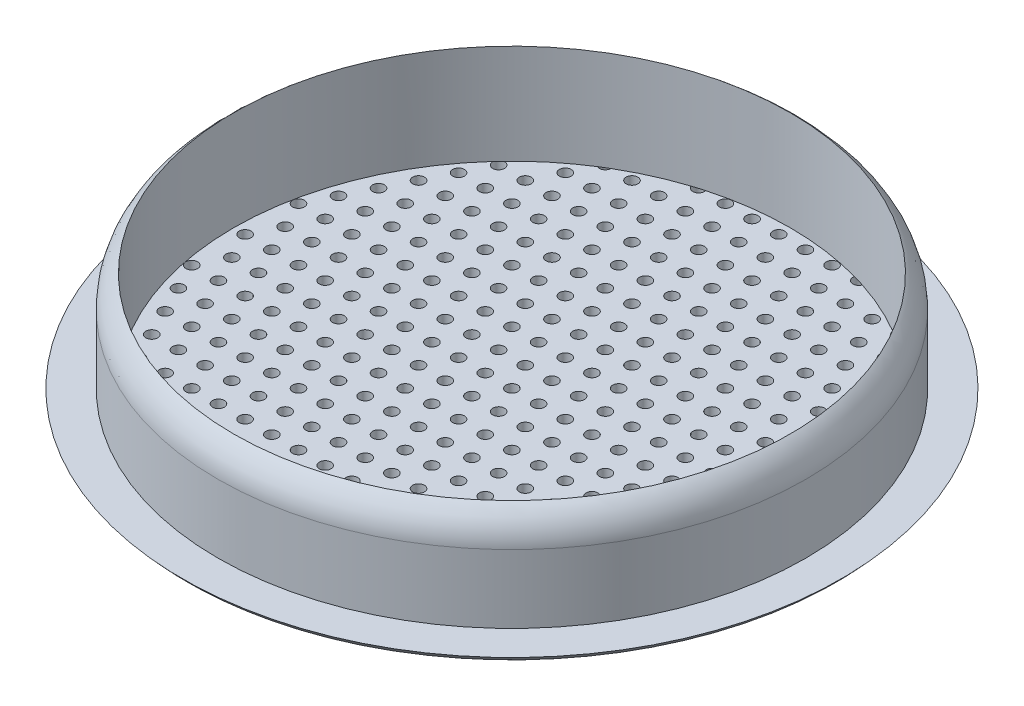
SolidWorks part; units mm, degrees
ref_plane "Front Plane" through (0, 0, 0) normal (0, 0, 1) x (1, 0, 0)
ref_plane "Top Plane" through (0, 0, 0) normal (0, 1, 0) x (1, 0, 0)
ref_plane "Right Plane" through (0, 0, 0) normal (1, 0, 0) x (0, 0, -1)
sketch "Sketch2" plane through (0, 0, 0) normal (0, 0, 1) x (1, 0, 0)
  line L0 (-35.465, 0) -> (-35.465, 12.7)
  line L1 (-35.465, 12.7) -> (-37.465, 12.7)
  line L2 (-37.465, 12.7) -> (-37.465, 0)
  line L3 (-37.465, 0) -> (-42, 0)
  line L4 (-42, 0) -> (-42, -2)
  line L5 (-42, -2) -> (0, -2)
  line L6 (0, -2) -> (0, 0)
  line L7 (0, 0) -> (-35.465, 0)
  line L8 (0, 0) -> (0, 8.6226) construction
  dimension "D1" = 2
  dimension "D2" = 2
  dimension "D3" = 84
  dimension "D4" = 74.93
  dimension "D5" = 12.7
revolve "Revolve1" add sketch "Sketch2" angle 360 about L8
sketch "Sketch3" plane through (0, 0, 0) normal (0, 1, 0) x (1, 0, 0)
  line L0 (0, 0) -> (-24.0588, 0) construction
  line L1 (0, -10.2) -> (0, 10.2) construction
  circle A0 centre (0, 0) radius 0.75
  circle A1 centre (3.4, 0) radius 0.75
  circle A2 centre (6.8, 0) radius 0.75
  circle A3 centre (10.2, 0) radius 0.75
  circle A4 centre (13.6, 0) radius 0.75
  circle A5 centre (17, 0) radius 0.75
  circle A6 centre (20.4, 0) radius 0.75
  circle A7 centre (23.8, 0) radius 0.75
  circle A8 centre (27.2, 0) radius 0.75
  circle A9 centre (30.6, 0) radius 0.75
  circle A10 centre (34, 0) radius 0.75
  circle A11 centre (3.4, 6.8) radius 0.75
  circle A12 centre (6.8, 6.8) radius 0.75
  circle A13 centre (10.2, 6.8) radius 0.75
  circle A14 centre (13.6, 6.8) radius 0.75
  circle A15 centre (17, 6.8) radius 0.75
  circle A16 centre (20.4, 6.8) radius 0.75
  circle A17 centre (23.8, 6.8) radius 0.75
  circle A18 centre (27.2, 6.8) radius 0.75
  circle A19 centre (30.6, 6.8) radius 0.75
  circle A20 centre (34, 6.8) radius 0.75
  circle A21 centre (3.4, 13.6) radius 0.75
  circle A22 centre (6.8, 13.6) radius 0.75
  circle A23 centre (10.2, 13.6) radius 0.75
  circle A24 centre (13.6, 13.6) radius 0.75
  circle A25 centre (17, 13.6) radius 0.75
  circle A26 centre (20.4, 13.6) radius 0.75
  circle A27 centre (23.8, 13.6) radius 0.75
  circle A28 centre (27.2, 13.6) radius 0.75
  circle A29 centre (30.6, 13.6) radius 0.75
  circle A30 centre (34, 13.6) radius 0.75 [skipped]
  circle A31 centre (3.4, 20.4) radius 0.75
  circle A32 centre (6.8, 20.4) radius 0.75
  circle A33 centre (10.2, 20.4) radius 0.75
  circle A34 centre (13.6, 20.4) radius 0.75
  circle A35 centre (17, 20.4) radius 0.75
  circle A36 centre (20.4, 20.4) radius 0.75
  circle A37 centre (23.8, 20.4) radius 0.75
  circle A38 centre (27.2, 20.4) radius 0.75
  circle A40 centre (34, 20.4) radius 0.75 [skipped]
  circle A41 centre (3.4, 27.2) radius 0.75
  circle A42 centre (6.8, 27.2) radius 0.75
  circle A43 centre (10.2, 27.2) radius 0.75
  circle A44 centre (13.6, 27.2) radius 0.75
  circle A45 centre (17, 27.2) radius 0.75
  circle A46 centre (20.4, 27.2) radius 0.75
  circle A48 centre (27.2, 27.2) radius 0.75 [skipped]
  circle A49 centre (30.6, 27.2) radius 0.75 [skipped]
  circle A50 centre (34, 27.2) radius 0.75 [skipped]
  circle A51 centre (3.4, 34) radius 0.75
  circle A52 centre (6.8, 34) radius 0.75
  circle A53 centre (10.2, 34) radius 0.75
  circle A54 centre (13.6, 34) radius 0.75
  circle A55 centre (17, 34) radius 0.75 [skipped]
  circle A56 centre (20.4, 34) radius 0.75 [skipped]
  circle A57 centre (23.8, 34) radius 0.75 [skipped]
  circle A58 centre (27.2, 34) radius 0.75 [skipped]
  circle A59 centre (30.6, 34) radius 0.75 [skipped]
  circle A60 centre (34, 34) radius 0.75 [skipped]
  circle A61 centre (0, 6.8) radius 0.75
  circle A62 centre (0, 13.6) radius 0.75
  circle A63 centre (0, 20.4) radius 0.75
  circle A64 centre (0, 27.2) radius 0.75
  circle A65 centre (0, 34) radius 0.75
  circle A66 centre (1.7, 3.4) radius 0.75
  circle A67 centre (5.1, 3.4) radius 0.75
  circle A68 centre (8.5, 3.4) radius 0.75
  circle A69 centre (11.9, 3.4) radius 0.75
  circle A70 centre (15.3, 3.4) radius 0.75
  circle A71 centre (18.7, 3.4) radius 0.75
  circle A72 centre (22.1, 3.4) radius 0.75
  circle A73 centre (25.5, 3.4) radius 0.75
  circle A74 centre (28.9, 3.4) radius 0.75
  circle A75 centre (32.3, 3.4) radius 0.75
  circle A77 centre (5.1, 10.2) radius 0.75
  circle A78 centre (8.5, 10.2) radius 0.75
  circle A79 centre (11.9, 10.2) radius 0.75
  circle A80 centre (15.3, 10.2) radius 0.75
  circle A81 centre (18.7, 10.2) radius 0.75
  circle A82 centre (22.1, 10.2) radius 0.75
  circle A83 centre (25.5, 10.2) radius 0.75
  circle A84 centre (28.9, 10.2) radius 0.75
  circle A85 centre (32.3, 10.2) radius 0.75
  circle A87 centre (5.1, 17) radius 0.75
  circle A88 centre (8.5, 17) radius 0.75
  circle A89 centre (11.9, 17) radius 0.75
  circle A90 centre (15.3, 17) radius 0.75
  circle A91 centre (18.7, 17) radius 0.75
  circle A92 centre (22.1, 17) radius 0.75
  circle A93 centre (25.5, 17) radius 0.75
  circle A94 centre (28.9, 17) radius 0.75
  circle A97 centre (5.1, 23.8) radius 0.75
  circle A98 centre (8.5, 23.8) radius 0.75
  circle A99 centre (11.9, 23.8) radius 0.75
  circle A100 centre (15.3, 23.8) radius 0.75
  circle A101 centre (18.7, 23.8) radius 0.75
  circle A102 centre (22.1, 23.8) radius 0.75
  circle A103 centre (25.5, 23.8) radius 0.75
  circle A107 centre (5.1, 30.6) radius 0.75
  circle A108 centre (8.5, 30.6) radius 0.75
  circle A109 centre (11.9, 30.6) radius 0.75
  circle A110 centre (15.3, 30.6) radius 0.75
  circle A111 centre (18.7, 30.6) radius 0.75
  circle A117 centre (1.7, 10.2) radius 0.75
  circle A118 centre (1.7, 17) radius 0.75
  circle A119 centre (1.7, 23.8) radius 0.75
  circle A120 centre (1.7, 30.6) radius 0.75
  circle A121 centre (35.7, 3.4) radius 0.75 [skipped]
  circle A122 centre (35.7, 10.2) radius 0.75 [skipped]
  circle A123 centre (32.3, 17) radius 0.75 [skipped]
  circle A124 centre (35.7, 17) radius 0.75 [skipped]
  circle A125 centre (32.3, 23.8) radius 0.75 [skipped]
  circle A126 centre (35.7, 23.8) radius 0.75 [skipped]
  circle A127 centre (32.3, 30.6) radius 0.75 [skipped]
  circle A128 centre (35.7, 30.6) radius 0.75 [skipped]
  circle A129 centre (25.5, 30.6) radius 0.75 [skipped]
  circle A130 centre (28.9, 30.6) radius 0.75 [skipped]
  circle A131 centre (30.6, 20.4) radius 0.75 [skipped]
  circle A132 centre (28.9, 23.8) radius 0.75 [skipped]
  circle A133 centre (23.8, 27.2) radius 0.75 [skipped]
  circle A134 centre (22.1, 30.6) radius 0.75 [skipped]
  circle A135 centre (-1.7, 30.6) radius 0.75
  circle A136 centre (-1.7, 23.8) radius 0.75
  circle A137 centre (-1.7, 17) radius 0.75
  circle A138 centre (-1.7, 10.2) radius 0.75
  circle A139 centre (-18.7, 30.6) radius 0.75
  circle A140 centre (-15.3, 30.6) radius 0.75
  circle A141 centre (-11.9, 30.6) radius 0.75
  circle A142 centre (-8.5, 30.6) radius 0.75
  circle A143 centre (-5.1, 30.6) radius 0.75
  circle A144 centre (-25.5, 23.8) radius 0.75
  circle A145 centre (-22.1, 23.8) radius 0.75
  circle A146 centre (-18.7, 23.8) radius 0.75
  circle A147 centre (-15.3, 23.8) radius 0.75
  circle A148 centre (-11.9, 23.8) radius 0.75
  circle A149 centre (-8.5, 23.8) radius 0.75
  circle A150 centre (-5.1, 23.8) radius 0.75
  circle A151 centre (-28.9, 17) radius 0.75
  circle A152 centre (-25.5, 17) radius 0.75
  circle A153 centre (-22.1, 17) radius 0.75
  circle A154 centre (-18.7, 17) radius 0.75
  circle A155 centre (-15.3, 17) radius 0.75
  circle A156 centre (-11.9, 17) radius 0.75
  circle A157 centre (-8.5, 17) radius 0.75
  circle A158 centre (-5.1, 17) radius 0.75
  circle A159 centre (-32.3, 10.2) radius 0.75
  circle A160 centre (-28.9, 10.2) radius 0.75
  circle A161 centre (-25.5, 10.2) radius 0.75
  circle A162 centre (-22.1, 10.2) radius 0.75
  circle A163 centre (-18.7, 10.2) radius 0.75
  circle A164 centre (-15.3, 10.2) radius 0.75
  circle A165 centre (-11.9, 10.2) radius 0.75
  circle A166 centre (-8.5, 10.2) radius 0.75
  circle A167 centre (-5.1, 10.2) radius 0.75
  circle A168 centre (-32.3, 3.4) radius 0.75
  circle A169 centre (-28.9, 3.4) radius 0.75
  circle A170 centre (-25.5, 3.4) radius 0.75
  circle A171 centre (-22.1, 3.4) radius 0.75
  circle A172 centre (-18.7, 3.4) radius 0.75
  circle A173 centre (-15.3, 3.4) radius 0.75
  circle A174 centre (-11.9, 3.4) radius 0.75
  circle A175 centre (-8.5, 3.4) radius 0.75
  circle A176 centre (-5.1, 3.4) radius 0.75
  circle A177 centre (-1.7, 3.4) radius 0.75
  circle A178 centre (-13.6, 34) radius 0.75
  circle A179 centre (-10.2, 34) radius 0.75
  circle A180 centre (-6.8, 34) radius 0.75
  circle A181 centre (-3.4, 34) radius 0.75
  circle A182 centre (-20.4, 27.2) radius 0.75
  circle A183 centre (-17, 27.2) radius 0.75
  circle A184 centre (-13.6, 27.2) radius 0.75
  circle A185 centre (-10.2, 27.2) radius 0.75
  circle A186 centre (-6.8, 27.2) radius 0.75
  circle A187 centre (-3.4, 27.2) radius 0.75
  circle A188 centre (-27.2, 20.4) radius 0.75
  circle A189 centre (-23.8, 20.4) radius 0.75
  circle A190 centre (-20.4, 20.4) radius 0.75
  circle A191 centre (-17, 20.4) radius 0.75
  circle A192 centre (-13.6, 20.4) radius 0.75
  circle A193 centre (-10.2, 20.4) radius 0.75
  circle A194 centre (-6.8, 20.4) radius 0.75
  circle A195 centre (-3.4, 20.4) radius 0.75
  circle A196 centre (-30.6, 13.6) radius 0.75
  circle A197 centre (-27.2, 13.6) radius 0.75
  circle A198 centre (-23.8, 13.6) radius 0.75
  circle A199 centre (-20.4, 13.6) radius 0.75
  circle A200 centre (-17, 13.6) radius 0.75
  circle A201 centre (-13.6, 13.6) radius 0.75
  circle A202 centre (-10.2, 13.6) radius 0.75
  circle A203 centre (-6.8, 13.6) radius 0.75
  circle A204 centre (-3.4, 13.6) radius 0.75
  circle A205 centre (-34, 6.8) radius 0.75
  circle A206 centre (-30.6, 6.8) radius 0.75
  circle A207 centre (-27.2, 6.8) radius 0.75
  circle A208 centre (-23.8, 6.8) radius 0.75
  circle A209 centre (-20.4, 6.8) radius 0.75
  circle A210 centre (-17, 6.8) radius 0.75
  circle A211 centre (-13.6, 6.8) radius 0.75
  circle A212 centre (-10.2, 6.8) radius 0.75
  circle A213 centre (-6.8, 6.8) radius 0.75
  circle A214 centre (-3.4, 6.8) radius 0.75
  circle A215 centre (-34, 0) radius 0.75
  circle A216 centre (-30.6, 0) radius 0.75
  circle A217 centre (-27.2, 0) radius 0.75
  circle A218 centre (-23.8, 0) radius 0.75
  circle A219 centre (-20.4, 0) radius 0.75
  circle A220 centre (-17, 0) radius 0.75
  circle A221 centre (-13.6, 0) radius 0.75
  circle A222 centre (-10.2, 0) radius 0.75
  circle A223 centre (-6.8, 0) radius 0.75
  circle A224 centre (-3.4, 0) radius 0.75
  circle A225 centre (-3.4, -6.8) radius 0.75
  circle A226 centre (-6.8, -6.8) radius 0.75
  circle A227 centre (-10.2, -6.8) radius 0.75
  circle A228 centre (-13.6, -6.8) radius 0.75
  circle A229 centre (-17, -6.8) radius 0.75
  circle A230 centre (-20.4, -6.8) radius 0.75
  circle A231 centre (-23.8, -6.8) radius 0.75
  circle A232 centre (-27.2, -6.8) radius 0.75
  circle A233 centre (-30.6, -6.8) radius 0.75
  circle A234 centre (-34, -6.8) radius 0.75
  circle A235 centre (-3.4, -13.6) radius 0.75
  circle A236 centre (-6.8, -13.6) radius 0.75
  circle A237 centre (-10.2, -13.6) radius 0.75
  circle A238 centre (-13.6, -13.6) radius 0.75
  circle A239 centre (-17, -13.6) radius 0.75
  circle A240 centre (-20.4, -13.6) radius 0.75
  circle A241 centre (-23.8, -13.6) radius 0.75
  circle A242 centre (-27.2, -13.6) radius 0.75
  circle A243 centre (-30.6, -13.6) radius 0.75
  circle A244 centre (-3.4, -20.4) radius 0.75
  circle A245 centre (-6.8, -20.4) radius 0.75
  circle A246 centre (-10.2, -20.4) radius 0.75
  circle A247 centre (-13.6, -20.4) radius 0.75
  circle A248 centre (-17, -20.4) radius 0.75
  circle A249 centre (-20.4, -20.4) radius 0.75
  circle A250 centre (-23.8, -20.4) radius 0.75
  circle A251 centre (-27.2, -20.4) radius 0.75
  circle A252 centre (-3.4, -27.2) radius 0.75
  circle A253 centre (-6.8, -27.2) radius 0.75
  circle A254 centre (-10.2, -27.2) radius 0.75
  circle A255 centre (-13.6, -27.2) radius 0.75
  circle A256 centre (-17, -27.2) radius 0.75
  circle A257 centre (-20.4, -27.2) radius 0.75
  circle A258 centre (-3.4, -34) radius 0.75
  circle A259 centre (-6.8, -34) radius 0.75
  circle A260 centre (-10.2, -34) radius 0.75
  circle A261 centre (-13.6, -34) radius 0.75
  circle A262 centre (-1.7, -3.4) radius 0.75
  circle A263 centre (-5.1, -3.4) radius 0.75
  circle A264 centre (-8.5, -3.4) radius 0.75
  circle A265 centre (-11.9, -3.4) radius 0.75
  circle A266 centre (-15.3, -3.4) radius 0.75
  circle A267 centre (-18.7, -3.4) radius 0.75
  circle A268 centre (-22.1, -3.4) radius 0.75
  circle A269 centre (-25.5, -3.4) radius 0.75
  circle A270 centre (-28.9, -3.4) radius 0.75
  circle A271 centre (-32.3, -3.4) radius 0.75
  circle A272 centre (-5.1, -10.2) radius 0.75
  circle A273 centre (-8.5, -10.2) radius 0.75
  circle A274 centre (-11.9, -10.2) radius 0.75
  circle A275 centre (-15.3, -10.2) radius 0.75
  circle A276 centre (-18.7, -10.2) radius 0.75
  circle A277 centre (-22.1, -10.2) radius 0.75
  circle A278 centre (-25.5, -10.2) radius 0.75
  circle A279 centre (-28.9, -10.2) radius 0.75
  circle A280 centre (-32.3, -10.2) radius 0.75
  circle A281 centre (-5.1, -17) radius 0.75
  circle A282 centre (-8.5, -17) radius 0.75
  circle A283 centre (-11.9, -17) radius 0.75
  circle A284 centre (-15.3, -17) radius 0.75
  circle A285 centre (-18.7, -17) radius 0.75
  circle A286 centre (-22.1, -17) radius 0.75
  circle A287 centre (-25.5, -17) radius 0.75
  circle A288 centre (-28.9, -17) radius 0.75
  circle A289 centre (-5.1, -23.8) radius 0.75
  circle A290 centre (-8.5, -23.8) radius 0.75
  circle A291 centre (-11.9, -23.8) radius 0.75
  circle A292 centre (-15.3, -23.8) radius 0.75
  circle A293 centre (-18.7, -23.8) radius 0.75
  circle A294 centre (-22.1, -23.8) radius 0.75
  circle A295 centre (-25.5, -23.8) radius 0.75
  circle A296 centre (-5.1, -30.6) radius 0.75
  circle A297 centre (-8.5, -30.6) radius 0.75
  circle A298 centre (-11.9, -30.6) radius 0.75
  circle A299 centre (-15.3, -30.6) radius 0.75
  circle A300 centre (-18.7, -30.6) radius 0.75
  circle A301 centre (-1.7, -10.2) radius 0.75
  circle A302 centre (-1.7, -17) radius 0.75
  circle A303 centre (-1.7, -23.8) radius 0.75
  circle A304 centre (-1.7, -30.6) radius 0.75
  circle A305 centre (1.7, -30.6) radius 0.75
  circle A306 centre (1.7, -23.8) radius 0.75
  circle A307 centre (1.7, -17) radius 0.75
  circle A308 centre (1.7, -10.2) radius 0.75
  circle A309 centre (18.7, -30.6) radius 0.75
  circle A310 centre (15.3, -30.6) radius 0.75
  circle A311 centre (11.9, -30.6) radius 0.75
  circle A312 centre (8.5, -30.6) radius 0.75
  circle A313 centre (5.1, -30.6) radius 0.75
  circle A314 centre (25.5, -23.8) radius 0.75
  circle A315 centre (22.1, -23.8) radius 0.75
  circle A316 centre (18.7, -23.8) radius 0.75
  circle A317 centre (15.3, -23.8) radius 0.75
  circle A318 centre (11.9, -23.8) radius 0.75
  circle A319 centre (8.5, -23.8) radius 0.75
  circle A320 centre (5.1, -23.8) radius 0.75
  circle A321 centre (28.9, -17) radius 0.75
  circle A322 centre (25.5, -17) radius 0.75
  circle A323 centre (22.1, -17) radius 0.75
  circle A324 centre (18.7, -17) radius 0.75
  circle A325 centre (15.3, -17) radius 0.75
  circle A326 centre (11.9, -17) radius 0.75
  circle A327 centre (8.5, -17) radius 0.75
  circle A328 centre (5.1, -17) radius 0.75
  circle A329 centre (32.3, -10.2) radius 0.75
  circle A330 centre (28.9, -10.2) radius 0.75
  circle A331 centre (25.5, -10.2) radius 0.75
  circle A332 centre (22.1, -10.2) radius 0.75
  circle A333 centre (18.7, -10.2) radius 0.75
  circle A334 centre (15.3, -10.2) radius 0.75
  circle A335 centre (11.9, -10.2) radius 0.75
  circle A336 centre (8.5, -10.2) radius 0.75
  circle A337 centre (5.1, -10.2) radius 0.75
  circle A338 centre (32.3, -3.4) radius 0.75
  circle A339 centre (28.9, -3.4) radius 0.75
  circle A340 centre (25.5, -3.4) radius 0.75
  circle A341 centre (22.1, -3.4) radius 0.75
  circle A342 centre (18.7, -3.4) radius 0.75
  circle A343 centre (15.3, -3.4) radius 0.75
  circle A344 centre (11.9, -3.4) radius 0.75
  circle A345 centre (8.5, -3.4) radius 0.75
  circle A346 centre (5.1, -3.4) radius 0.75
  circle A347 centre (1.7, -3.4) radius 0.75
  circle A348 centre (0, -34) radius 0.75
  circle A349 centre (0, -27.2) radius 0.75
  circle A350 centre (0, -20.4) radius 0.75
  circle A351 centre (0, -13.6) radius 0.75
  circle A352 centre (0, -6.8) radius 0.75
  circle A353 centre (13.6, -34) radius 0.75
  circle A354 centre (10.2, -34) radius 0.75
  circle A355 centre (6.8, -34) radius 0.75
  circle A356 centre (3.4, -34) radius 0.75
  circle A357 centre (20.4, -27.2) radius 0.75
  circle A358 centre (17, -27.2) radius 0.75
  circle A359 centre (13.6, -27.2) radius 0.75
  circle A360 centre (10.2, -27.2) radius 0.75
  circle A361 centre (6.8, -27.2) radius 0.75
  circle A362 centre (3.4, -27.2) radius 0.75
  circle A363 centre (27.2, -20.4) radius 0.75
  circle A364 centre (23.8, -20.4) radius 0.75
  circle A365 centre (20.4, -20.4) radius 0.75
  circle A366 centre (17, -20.4) radius 0.75
  circle A367 centre (13.6, -20.4) radius 0.75
  circle A368 centre (10.2, -20.4) radius 0.75
  circle A369 centre (6.8, -20.4) radius 0.75
  circle A370 centre (3.4, -20.4) radius 0.75
  circle A371 centre (30.6, -13.6) radius 0.75
  circle A372 centre (27.2, -13.6) radius 0.75
  circle A373 centre (23.8, -13.6) radius 0.75
  circle A374 centre (20.4, -13.6) radius 0.75
  circle A375 centre (17, -13.6) radius 0.75
  circle A376 centre (13.6, -13.6) radius 0.75
  circle A377 centre (10.2, -13.6) radius 0.75
  circle A378 centre (6.8, -13.6) radius 0.75
  circle A379 centre (3.4, -13.6) radius 0.75
  circle A380 centre (34, -6.8) radius 0.75
  circle A381 centre (30.6, -6.8) radius 0.75
  circle A382 centre (27.2, -6.8) radius 0.75
  circle A383 centre (23.8, -6.8) radius 0.75
  circle A384 centre (20.4, -6.8) radius 0.75
  circle A385 centre (17, -6.8) radius 0.75
  circle A386 centre (13.6, -6.8) radius 0.75
  circle A387 centre (10.2, -6.8) radius 0.75
  circle A388 centre (6.8, -6.8) radius 0.75
  circle A389 centre (3.4, -6.8) radius 0.75
  dimension "D1" = 1.5
  dimension "D4" = 1.5
  dimension "D5" = 3.4
  dimension "D6" = 1.7
  dimension "D2" = 11
  dimension "D3" = 6
  dimension "D7" = 11
  dimension "D8" = 5
extrude "Cut-Extrude1" cut sketch "Sketch3" against normal up to next (2 mm away)
fillet "Fillet1" radius 5 2 edges at (0, -2, -42) (0, 12.7, -37.465)
